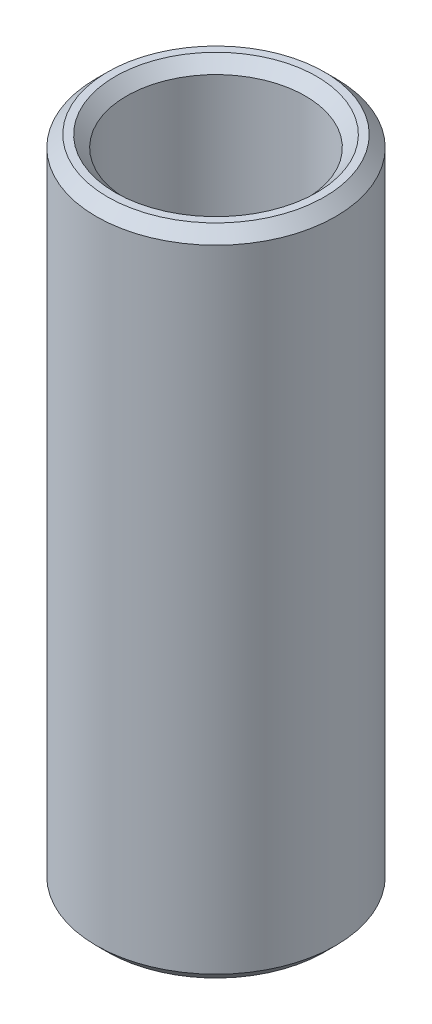
SolidWorks part; units mm, degrees
ref_plane "Front Plane" through (0, 0, 0) normal (0, 0, 1) x (1, 0, 0)
ref_plane "Top Plane" through (0, 0, 0) normal (0, 1, 0) x (1, 0, 0)
ref_plane "Right Plane" through (0, 0, 0) normal (1, 0, 0) x (0, 0, -1)
sketch "Sketch1" plane through (0, 0, 0) normal (0, 1, 0) x (1, 0, 0)
  circle A0 centre (0, 0) radius 22.5
  dimension "SLEEVE_OD" = 45
extrude "Boss-Extrude1" add sketch "Sketch1" along normal blind 122.9552
sketch "Sketch2" plane through (0, 0, 0) normal (0, 1, 0) x (1, 0, 0)
  circle A0 centre (0, 0) radius 16.8048
  dimension "BORE_D" = 33.6096
extrude "Cut-Extrude1" cut sketch "Sketch2" along normal through all
chamfer "Chamfer1" distance 2.1265 angle 45 4 edges at (0, 122.9552, 16.8048) (0, 0, 16.8048) (0, 0, 22.5) (0, 122.9552, 22.5)
